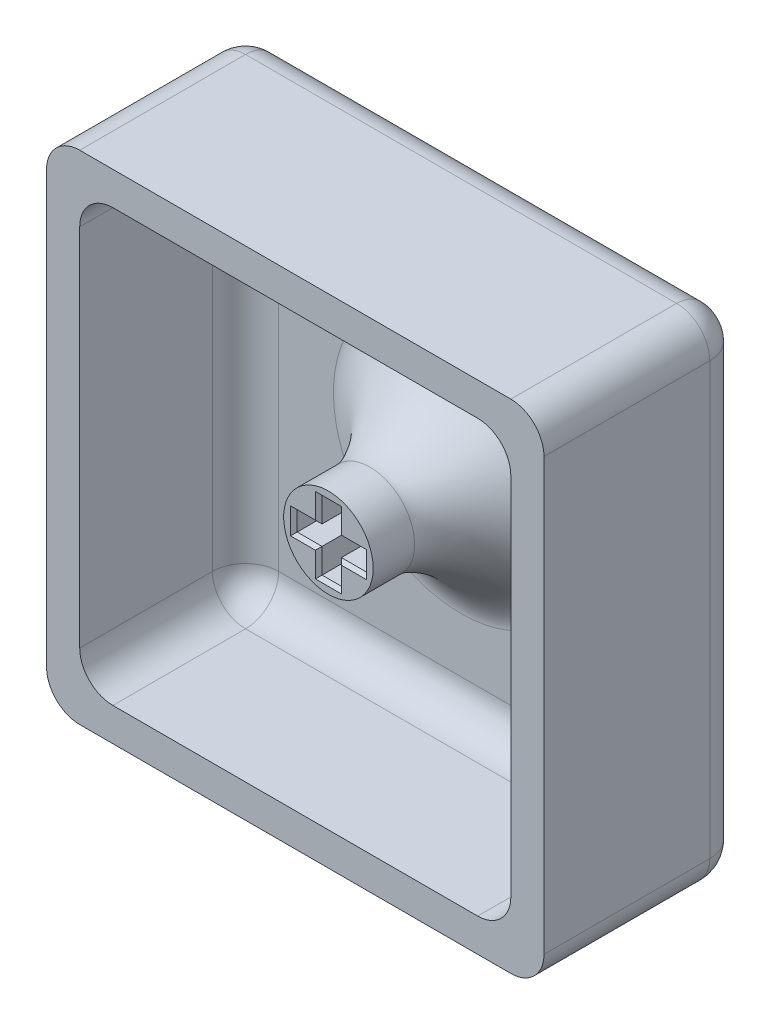
SolidWorks part; units mm, degrees
other "标注1"
sketch "草图2" plane through (15, -15, 10) normal (0.3933, -0.7926, 0.466) x (0.9059, 0.4207, -0.0491)
ref_plane "前视基准面" through (0, 0, 0) normal (0, 0, 1) x (1, 0, 0)
ref_plane "上视基准面" through (0, 0, 0) normal (0, 1, 0) x (1, 0, 0)
ref_plane "右视基准面" through (0, 0, 0) normal (1, 0, 0) x (0, 0, -1)
sketch "草图1" plane through (0, 0, 0) normal (0, 0, 1) x (1, 0, 0)
  line L0 (-13, 15) -> (13, 15)
  line L1 (-11, 13) -> (11, 13)
  line L2 (-13, 11) -> (-13, -11)
  line L3 (-11, -13) -> (11, -13)
  line L4 (13, 11) -> (13, -11)
  line L5 (0, -13) -> (0, 13) construction
  line L6 (-13, 0) -> (13, 0) construction
  line L7 (15, 13) -> (15, -13)
  line L8 (-13, -15) -> (13, -15)
  line L9 (-15, 13) -> (-15, -13)
  line L10 (-13, -13) -> (13, -13) construction
  line L11 (-2.085, 0.585) -> (2.085, 0.585)
  line L12 (-2.085, 0.585) -> (-2.085, -0.585)
  line L13 (-2.085, -0.585) -> (2.085, -0.585)
  line L14 (2.085, 0.585) -> (2.085, -0.585)
  line L15 (0, -0.585) -> (0, 0.585) construction
  line L16 (-2.085, 0) -> (2.085, 0) construction
  line L17 (-0.585, 2.085) -> (0.585, 2.085)
  line L18 (-0.585, 2.085) -> (-0.585, -2.085)
  line L19 (-0.585, -2.085) -> (0.585, -2.085)
  line L20 (0.585, 2.085) -> (0.585, -2.085)
  line L21 (0, -2.085) -> (0, 2.085) construction
  line L22 (-0.585, 0) -> (0.585, 0) construction
  line L23 (13, 13) -> (13, -13) construction
  line L24 (-13, 13) -> (13, 13) construction
  line L25 (-13, 13) -> (-13, -13) construction
  line L26 (-15, 15) -> (-15, -15) construction
  line L27 (-15, -15) -> (15, -15) construction
  line L28 (15, 15) -> (15, -15) construction
  line L29 (-15, 15) -> (15, 15) construction
  line L36 (-13, 0) -> (-2.5, 0) construction
  circle A0 centre (0, 0) radius 2.7
  arc A1 (11, -13) -> (13, -11) centre (11, -11) ccw
  arc A2 (13, 11) -> (11, 13) centre (11, 11) ccw
  arc A3 (-13, 11) -> (-11, 13) centre (-11, 11) cw
  arc A4 (-13, -11) -> (-11, -13) centre (-11, -11) ccw
  arc A5 (-15, -13) -> (-13, -15) centre (-13, -13) ccw
  arc A6 (13, -15) -> (15, -13) centre (13, -13) ccw
  arc A7 (15, 13) -> (13, 15) centre (13, 13) ccw
  arc A8 (-15, 13) -> (-13, 15) centre (-13, 13) cw
  point P0 (0, 0)
  point P19 (13, -13)
  point P66 (0.0162, 0.0162)
  dimension "D4" = 5.4
  dimension "D9" = 2
  dimension "D1" = 30
  dimension "D2" = 30
  dimension "D5" = 4.17
  dimension "D6" = 1.17
  dimension "D7" = 4.17
  dimension "D8" = 1.17
  dimension "D3" = 2
extrude "凸台-拉伸1" add sketch "草图1" along normal blind 10 contours A8 L9 A5 L8 A6 L7 A7 L0 A4 L2 A3 L1 A2 L4 A1 L3 region at (0, 14.5757, 0)
extrude "凸台-拉伸2" add sketch "草图1<6>" along normal blind 8 separate body contours A0 L17 L20 L11 L14 L13 L19 L18 L12 region at (-2.6236, 0, 0)
sketch "草图1<6>" plane through (0, 0, 0) normal (0, 0, 1) x (1, 0, 0) same geometry as "草图1"
extrude "凸台-拉伸3" add sketch "草图1<7>" against normal blind 2 contours L8 A6 L7 A7 L0 A8 L9 A5
sketch "草图1<7>" plane through (0, 0, 0) normal (0, 0, 1) x (1, 0, 0) same geometry as "草图1"
fillet "圆角1" radius 2 8 edges at (-14.4142, 14.4142, -2) (-15, 0, -2) (-14.4142, -14.4142, -2) (0, -15, -2) (14.4142, -14.4142, -2) (15, 0, -2) (14.4142, 14.4142, -2) (0, 15, -2)
chamfer "倒角1" distance 0.2 angle 45 12 edges at (-0.585, 1.335, 8) (-1.335, 0.585, 8) (-2.085, 0, 8) (-1.335, -0.585, 8) (-0.585, -1.335, 8) (0, -2.085, 8) (0.585, -1.335, 8) (1.335, -0.585, 8) (2.085, 0, 8) (1.335, 0.585, 8) (0.585, 1.335, 8) (0, 2.085, 8)
fillet "圆角2" radius 2 8 edges at (-12.4142, -12.4142, 0) (-13, 0, 0) (-12.4142, 12.4142, 0) (0, 13, 0) (12.4142, 12.4142, 0) (13, 0, 0) (12.4142, -12.4142, 0) (0, -13, 0)
fillet "圆角3" radius 5 1 edges at (2.7, 0, 0) second distance 5.5 conic rho 0.25 first distance on face at (0, 0, 0)
